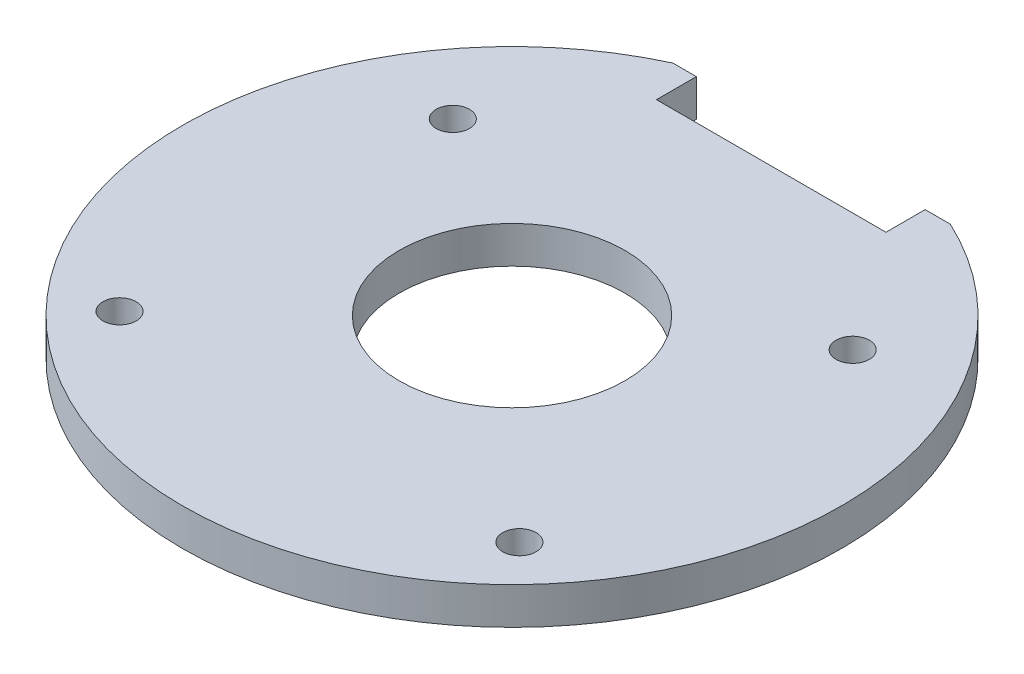
SolidWorks part; units mm, degrees
ref_plane "Спереди" through (0, 0, 0) normal (0, 0, 1) x (1, 0, 0)
ref_plane "Сверху" through (0, 0, 0) normal (0, 1, 0) x (1, 0, 0)
ref_plane "Справа" through (0, 0, 0) normal (1, 0, 0) x (0, 0, -1)
sketch "Эскиз2" plane through (0, 0, 0) normal (0, 1, 0) x (1, 0, 0)
  line L0 (-65, -26) -> (65, -26) construction
  line L1 (-65, 19) -> (65, 19) construction
  line L2 (-27, 50) -> (-27, -50) construction
  line L3 (27, 50) -> (27, -50) construction
  line L5 (-15.5, 35) -> (15.5, 35)
  line L7 (-15.5, 40.3935) -> (-15.5, 35)
  line L8 (15.5, 40.2863) -> (15.5, 35)
  line L9 (15.5, 40.2863) -> (18.9014, 40.2863)
  line L10 (-15.5, 40.3935) -> (-18.6713, 40.3935)
  arc A0 (-18.6713, 40.3935) -> (18.9014, 40.2863) centre (0, 0) ccw
  circle A2 centre (0, 0) radius 15.25
  circle A3 centre (-27, 19) radius 2.25
  circle A4 centre (27, 19) radius 2.25
  circle A5 centre (27, -26) radius 2.25
  circle A6 centre (-27, -26) radius 2.25
  point P2 (-27, 19.0221)
  point P21 (27, 19)
  point P25 (27, -26)
  point P28 (-27, -26)
extrude "Бобышка-Вытянуть1" add sketch "Эскиз2" along normal blind 5
